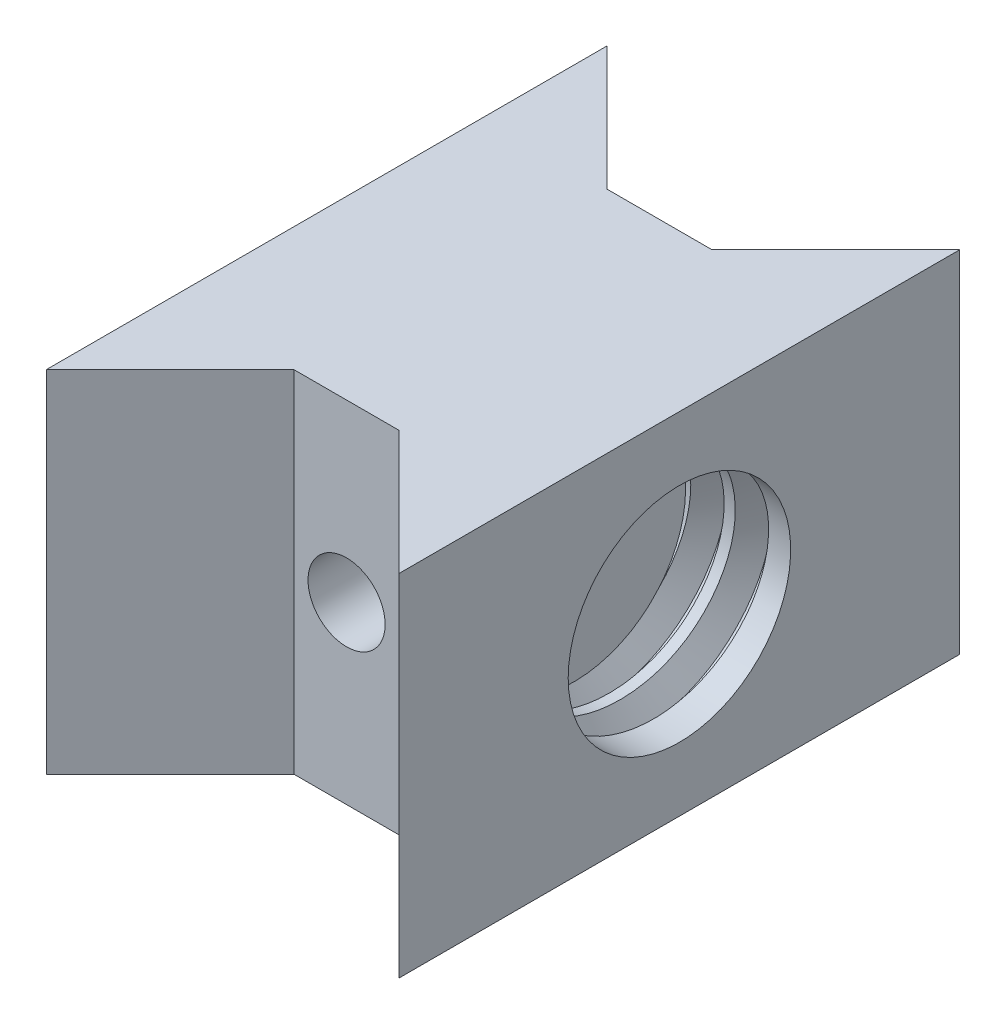
SolidWorks part; units mm, degrees
ref_plane "Front Plane" through (0, 0, 0) normal (0, 0, 1) x (1, 0, 0)
ref_plane "Top Plane" through (0, 0, 0) normal (0, 1, 0) x (1, 0, 0)
ref_plane "Right Plane" through (0, 0, 0) normal (1, 0, 0) x (0, 0, -1)
sketch "Sketch1" plane through (0, 0, 0) normal (0, 1, 0) x (1, 0, 0)
  line L0 (0, 0) -> (0, 8)
  line L1 (0, 0) -> (0, -8)
  line L2 (0, -8) -> (-3.5355, -4.4645)
  line L3 (0, 8) -> (-3.5355, 4.4645)
  line L5 (-3.5355, -4.4645) -> (-6.5355, -4.4645)
  line L6 (-3.5355, 4.4645) -> (-6.5355, 4.4645)
  line L7 (-6.5355, 4.4645) -> (-10.0711, 8)
  line L8 (-10.0711, 8) -> (-10.0711, -8)
  line L9 (-10.0711, -8) -> (-6.5355, -4.4645)
extrude "Boss-Extrude1" add sketch "Sketch1" along normal blind 10
sketch "Sketch3" plane through (0, 0, 0) normal (1, 0, 0) x (0, 0, -1)
  circle A0 centre (0, 5) radius 3.175
sketch "Sketch8" plane through (0, 0, 4.4645) normal (0, 0, 1) x (1, 0, 0)
  circle A0 centre (-5.0355, 5) radius 1.1
extrude "Cut-Extrude3" cut sketch "Sketch8" against normal through all
extrude "Cut-Extrude4" cut sketch "Sketch3" against normal blind 3
ref_plane "Plane4" through (-5.0355, 0, 0) normal (1, 0, 0) x (0, 0, -1)
mirror "Mirror2" about plane through (-5.0355, 0, 0) normal (1, 0, 0) of "Cut-Extrude4"
thread "Thread3" pitch 1.27 method cut profile "Thread Profile3" start angle 0, offset 0, length 3, pitch 1.27, diameter 6.35
ref_plane "Plane5" through (0, 5, 3.175) normal (0, -1, 0) x (0, 0, 1)
sketch "Thread Profile3" plane through (0, 5, 3.175) normal (0, -1, 0) x (0, 0, 1)
  line L0 (0, 0) -> (0, 1.27) construction
  line L1 (0, 0) -> (0.6874, 0.3969)
  line L2 (0.6874, 0.3969) -> (0.6874, 0.5556)
  line L3 (0.6874, 0.5556) -> (0, 0.9525)
  line L4 (0.6874, 0.4762) -> (0, 0.4762) construction
  line L11 (0, 0) -> (0, 0.9525)
  point P2 (0, 0)
  dimension "Pitch" = 1.27
  dimension "Profile_Angle" = 60
  dimension "Profile_Land" = 0.1588
  dimension "Profile_Height" = 0.6874
thread "Thread4" pitch 1.27 method cut profile "Thread Profile4" start angle 0, offset 0, length 3, pitch 1.27, diameter 6.35
ref_plane "Plane6" through (-10.0711, 5, -3.175) normal (0, -1, 0) x (0, 0, -1)
sketch "Thread Profile4" plane through (-10.0711, 5, -3.175) normal (0, -1, 0) x (0, 0, -1)
  line L0 (0, 0) -> (0, 1.27) construction
  line L1 (0, 0) -> (0.6874, 0.3969)
  line L2 (0.6874, 0.3969) -> (0.6874, 0.5556)
  line L3 (0.6874, 0.5556) -> (0, 0.9525)
  line L4 (0.6874, 0.4762) -> (0, 0.4762) construction
  line L11 (0, 0) -> (0, 0.9525)
  point P2 (0, 0)
  dimension "Pitch" = 1.27
  dimension "Profile_Angle" = 60
  dimension "Profile_Land" = 0.1588
  dimension "Profile_Height" = 0.6874
